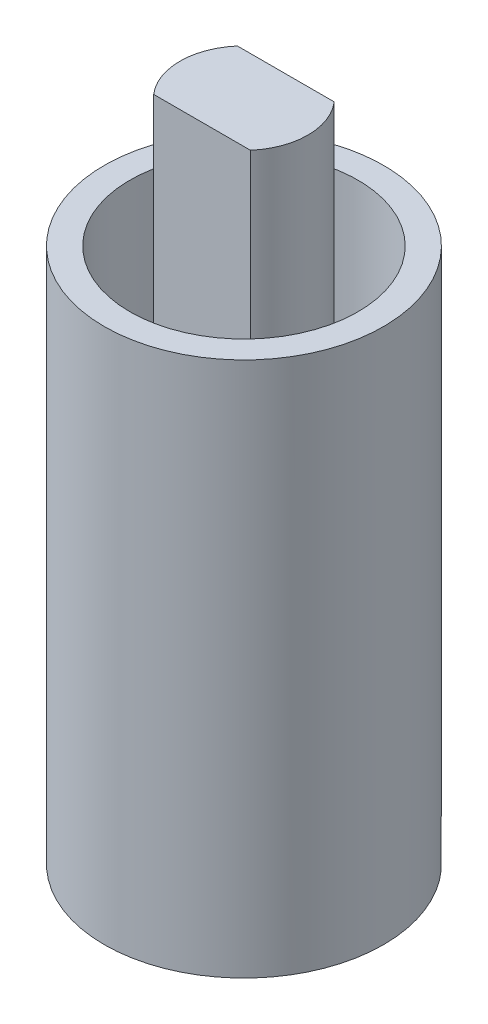
SolidWorks part; units mm, degrees
ref_plane "Front Plane" through (0, 0, 0) normal (0, 0, 1) x (1, 0, 0)
ref_plane "Top Plane" through (0, 0, 0) normal (0, 1, 0) x (1, 0, 0)
ref_plane "Right Plane" through (0, 0, 0) normal (1, 0, 0) x (0, 0, -1)
sketch "Sketch1" plane through (0, 0, 0) normal (0, 1, 0) x (1, 0, 0)
  circle A0 centre (0, 0) radius 2.75
  dimension "D1" = 5.5
extrude "Boss-Extrude1" add sketch "Sketch1" along normal blind 1.8
sketch "Sketch3" plane through (0, 1.8, 0) normal (0, 1, 0) x (1, 0, 0)
  line L0 (-2.0791, 1.8) -> (2.0791, 1.8)
  line L1 (-2.0791, -1.8) -> (2.0791, -1.8)
  arc A0 (-2.0791, 1.8) -> (-2.0791, -1.8) centre (0, 0) ccw
  arc A2 (2.0791, -1.8) -> (2.0791, 1.8) centre (0, 0) ccw
  dimension "D1" = 4.1581
extrude "Boss-Extrude2" add sketch "Sketch3" along normal blind 21.7
sketch "Sketch4" plane through (0, 0, 0) normal (0, -1, 0) x (1, 0, 0)
  circle A0 centre (0, 0) radius 6
  dimension "D1" = 12
extrude "Boss-Extrude3" add sketch "Sketch4" along normal blind 5
sketch "Sketch5" plane through (0, 0, 0) normal (0, 1, 0) x (1, 0, 0)
  circle A0 centre (0, 0) radius 4.9
  circle A1 centre (0, 0) radius 6
  circle A2 centre (0, 0) radius 6 construction
  dimension "D1" = 9.8
extrude "Boss-Extrude4" add sketch "Sketch5" along normal blind 18
